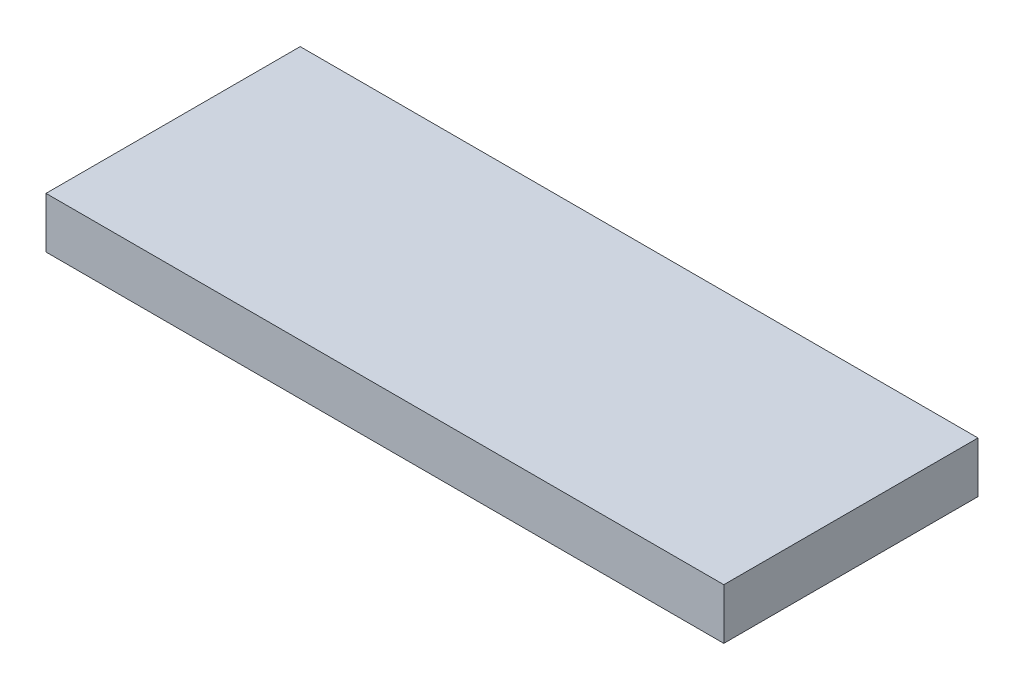
SolidWorks part; units mm, degrees
ref_plane "Front Plane" through (0, 0, 0) normal (0, 0, 1) x (1, 0, 0)
ref_plane "Top Plane" through (0, 0, 0) normal (0, 1, 0) x (1, 0, 0)
ref_plane "Right Plane" through (0, 0, 0) normal (1, 0, 0) x (0, 0, -1)
sketch "Sketch1" plane through (0, 0, 0) normal (0, 0, 1) x (1, 0, 0)
  line L0 (-3.18, 50.2599) -> (-3.18, 43.7299)
  line L2 (-20, -16.2701) -> (20, -16.2701)
  line L4 (-20, -16.2701) -> (-20, -81.2954)
  line L9 (-3.18, 43.7299) -> (3.18, 43.7299)
  line L11 (-85, -81.2954) -> (-20, -81.2954)
  line L12 (20, -16.2701) -> (20, -81.2954)
  line L13 (20, -81.2954) -> (85, -81.2954)
  line L39 (0, 55) -> (0, -81.2954)
  line L41 (0, -81.2954) -> (75, -81.2954)
  line L51 (71.3723, -70) -> (85, -70)
  line L63 (85, -70) -> (85, -10)
  line L64 (75, 0) -> (60, 0)
  line L65 (60, 0) -> (60, 45)
  line L66 (50, 55) -> (10, 55)
  line L67 (10, 55) -> (0, 55)
  line L173 (75, -81.2954) -> (75, -72.0944)
  line L175 (75, -72.0944) -> (71.3723, -70)
  arc A13 (85, -10) -> (75, 0) centre (75, -10) ccw
  arc A14 (60, 45) -> (50, 55) centre (50, 45) ccw
  circle A20 centre (30, 50) radius 1.52
  circle A21 centre (-30, 50) radius 1.52
  circle A22 centre (-62.5, -5) radius 1.52
  circle A23 centre (-80, -35) radius 1.52
  circle A24 centre (-62.5, -70.6477) radius 1.52
  circle A25 centre (62.5, -70.6477) radius 1.52
  circle A26 centre (80, -35) radius 1.52
  circle A27 centre (62.5, -5) radius 1.52
extrude "Boss-Extrude1" add sketch "Sketch1" along normal blind 2 rebuild error yes
sketch "Sketch2" plane through (0, 0, 0) normal (0, 0, -1) x (-1, 0, 0)
  line L0 (20, -60.0001) -> (20, -10.0001) construction
  line L1 (-20, -16.2701) -> (20, -16.2701)
  line L2 (-20, -16.2701) -> (-20, -13.2701)
  line L3 (-20, -13.2701) -> (20, -13.2701)
  line L4 (20, -16.2701) -> (20, -13.2701)
  dimension "D1" = 3
extrude "Boss-Extrude2" add sketch "Sketch2" along normal blind 15
